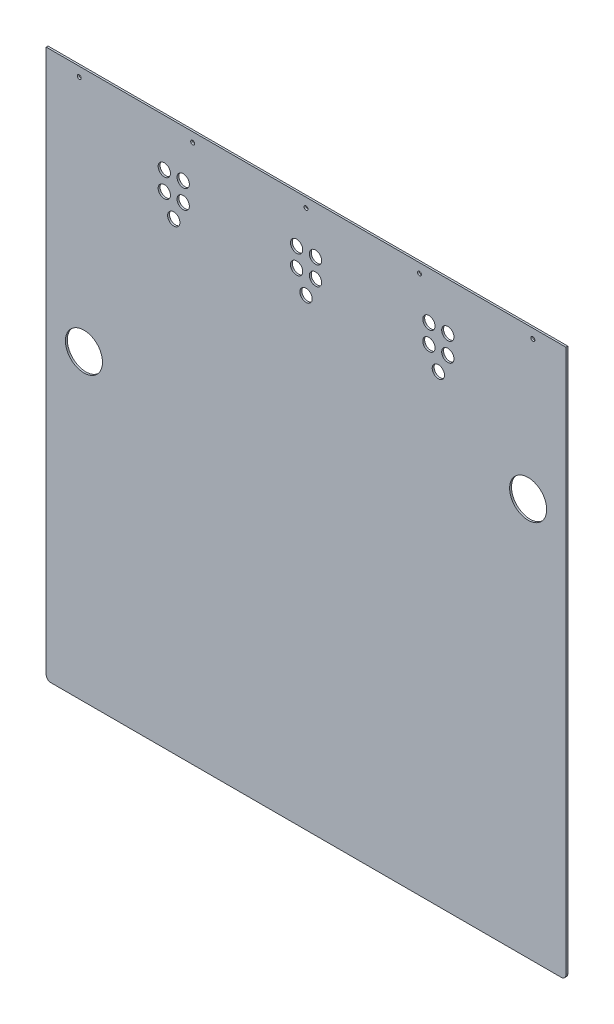
SolidWorks part; units mm, degrees
ref_plane "Płaszczyzna przednia" through (0, 0, 0) normal (0, 0, 1) x (1, 0, 0)
ref_plane "Płaszczyzna górna" through (0, 0, 0) normal (0, 1, 0) x (1, 0, 0)
ref_plane "Płaszczyzna prawa" through (0, 0, 0) normal (1, 0, 0) x (0, 0, -1)
sketch "Szkic1" plane through (0, 0, 0) normal (0, 0, 1) x (1, 0, 0)
  line L1 (-275, -290) -> (275, -290)
  line L2 (-275, -290) -> (-275, 290)
  line L3 (-275, 290) -> (275, 290)
  line L4 (275, -290) -> (275, 290)
  line L5 (-275, -290) -> (275, 290) construction
  line L6 (-275, 290) -> (275, -290) construction
  point P0 (0, 0)
  dimension "D1" = 580
  dimension "D2" = 550
base flange "Odgięcie bazowe1" sketch "Szkic1" thickness 2 reverse thickness direction no parameters "D1"=0.7366
fillet "Zaokrąglenie1" radius 5 2 edges at (-275, -290, -1) (275, -290, -1)
sketch "Szkic2" plane through (0, 0, 0) normal (0, 0, 1) x (1, 0, 0)
  line L0 (-275, 290) -> (-275, -285) construction
  line L1 (-270, -290) -> (270, -290) construction
  line L2 (275, -285) -> (275, 290) construction
  circle A0 centre (-235, 31) radius 19.6
  circle A1 centre (235, 131) radius 19.6
  dimension "D1" = 39.2
  dimension "D4" = 40
  dimension "34" = 39.2
  dimension "D2" = 40
  dimension "D3" = 321
  dimension "D5" = 421
extrude "Wytnij-wyciągnięcie1" cut sketch "Szkic2" against normal up to next normal cut yes
sketch "Szkic4" plane through (0, 0, 0) normal (0, 0, 1) x (1, 0, 0)
  line L0 (0, 0) -> (0, 290) construction
  line L1 (275, 290) -> (-275, 290) construction
  circle A0 centre (0, 280) radius 2.1
  circle A1 centre (120, 280) radius 2.1
  circle A2 centre (240, 280) radius 2.1
  circle A3 centre (-240, 280) radius 2.1
  circle A4 centre (-120, 280) radius 2.1
  dimension "D1" = 10
  dimension "D2" = 4.2
  dimension "D3" = 3
extrude "Wytnij-wyciągnięcie3" cut sketch "Szkic4" against normal up to next normal cut yes
sketch "Szkic5" plane through (0, 0, -2) normal (0, 0, -1) x (-1, 0, 0)
  line L0 (-275, 240) -> (275, 240) construction
  line L1 (-275, -285) -> (-275, 290) construction
  line L2 (275, 290) -> (275, -285) construction
  line L3 (-275, 290) -> (275, 290) construction
  line L4 (-275, 220) -> (275, 220) construction
  line L5 (0, 290) -> (0, -290) construction
  line L6 (270, -290) -> (-270, -290) construction
  circle A0 centre (10, 240) radius 6.5
  circle A1 centre (10, 220) radius 6.5
  circle A2 centre (-10, 220) radius 6.5
  circle A3 centre (-10, 240) radius 6.5
  circle A4 centre (130, 240) radius 6.5
  circle A5 centre (150, 240) radius 6.5
  circle A6 centre (130, 220) radius 6.5
  circle A7 centre (150, 220) radius 6.5
  circle A8 centre (-130, 220) radius 6.5
  circle A9 centre (-150, 220) radius 6.5
  circle A10 centre (-150, 240) radius 6.5
  circle A11 centre (-130, 240) radius 6.5
  circle A12 centre (-10, 220) radius 6.5
  circle A13 centre (10, 220) radius 6.5
  circle A14 centre (-10, 240) radius 6.5
  circle A15 centre (10, 240) radius 6.5
  point P14 (0, -290)
  point P15 (0, 290)
  dimension "D4" = 13
  dimension "D5" = 13
  dimension "D1" = 50
  dimension "D2" = 20
  dimension "D3" = 10
  dimension "D6" = 10
  dimension "D7" = 2
extrude "Wytnij-wyciągnięcie4" cut sketch "Szkic5" against normal up to next contours A10 | A11 | A9 | A8 | A0 | A1 | A2 | A6 | A7 | A5 | A4 | A3 normal cut yes
sketch "Szkic6" plane through (0, 0, -2) normal (0, 0, -1) x (-1, 0, 0)
  line L0 (-275, 200) -> (275, 200) construction
  line L1 (-275, -285) -> (-275, 290) construction
  line L2 (275, 290) -> (275, -285) construction
  line L3 (-275, 290) -> (275, 290) construction
  circle A0 centre (0, 200) radius 6.5
  circle A1 centre (140, 200) radius 6.5
  circle A2 centre (-140, 200) radius 6.5
  dimension "D2" = 13
  dimension "D1" = 90
  dimension "D3" = 2
  dimension "D4" = 2
extrude "Wytnij-wyciągnięcie5" cut sketch "Szkic6" against normal up to next normal cut yes
sketch "Linie zgięcia1" [suppressed] plane through (0, 0, 0) normal (0, 1, 0) x (1, 0, 0)
sketch "Ramka-graniczna1" [suppressed] plane through (0, 0, 0) normal (0, 1, 0) x (1, 0, 0)
sheet metal parameters "Arkusz blachy1" thickness 2 parameters "D1"=0.7366
flat pattern "Rozłożony model1" [suppressed]
sketch "Linie zgięcia2" plane through (0, 0, 0) normal (0, 1, 0) x (1, 0, 0)
sketch3d "Ramka-graniczna2" [suppressed]
  line L0 (265, -290, 0) -> (265, 290, 0) construction
  line L1 (-265, -290, 0) -> (-265, 290, 0) construction
  line L2 (265, -290, 0) -> (-265, -290, 0) construction
  line L3 (265, 290, 0) -> (-265, 290, 0) construction
sheet metal parameters "Arkusz blachy2" thickness 2 parameters "D1"=0.7366
flat pattern "Rozłożony model1"
sketch "Linie zgięcia2" plane through (0, 0, 0) normal (0, 1, 0) x (1, 0, 0)
sketch3d "Ramka-graniczna2" [suppressed]
  line L0 (275, -290, 0) -> (275, 290, 0) construction
  line L1 (-275, -290, 0) -> (-275, 290, 0) construction
  line L2 (275, -290, 0) -> (-275, -290, 0) construction
  line L3 (275, 290, 0) -> (-275, 290, 0) construction
sheet metal parameters "Arkusz blachy4" thickness 2 parameters "D1"=0.7366
flat pattern "Rozłożony model1"
sketch "Linie zgięcia2" plane through (0, 0, 0) normal (0, 1, 0) x (1, 0, 0)
sketch3d "Ramka-graniczna2" [suppressed]
  line L0 (275, -290, 0) -> (275, 290, 0) construction
  line L1 (-275, -290, 0) -> (-275, 290, 0) construction
  line L2 (275, -290, 0) -> (-275, -290, 0) construction
  line L3 (275, 290, 0) -> (-275, 290, 0) construction
sheet metal parameters "Arkusz blachy5" thickness 2 parameters "D1"=0.7366
flat pattern "Rozłożony model1"
sketch "Linie zgięcia2" plane through (0, 0, 0) normal (0, 1, 0) x (1, 0, 0)
sketch3d "Ramka-graniczna2" [suppressed]
  line L0 (275, -290, 0) -> (275, 290, 0) construction
  line L1 (-275, -290, 0) -> (-275, 290, 0) construction
  line L2 (275, -290, 0) -> (-275, -290, 0) construction
  line L3 (275, 290, 0) -> (-275, 290, 0) construction
sheet metal parameters "Arkusz blachy6" thickness 2 parameters "D1"=0.7366
flat pattern "Rozłożony model1"
sketch "Linie zgięcia2" plane through (0, 0, 0) normal (0, 1, 0) x (1, 0, 0)
sketch3d "Ramka-graniczna2" [suppressed]
  line L0 (275, -290, 0) -> (275, 290, 0) construction
  line L1 (-275, -290, 0) -> (-275, 290, 0) construction
  line L2 (275, -290, 0) -> (-275, -290, 0) construction
  line L3 (275, 290, 0) -> (-275, 290, 0) construction
